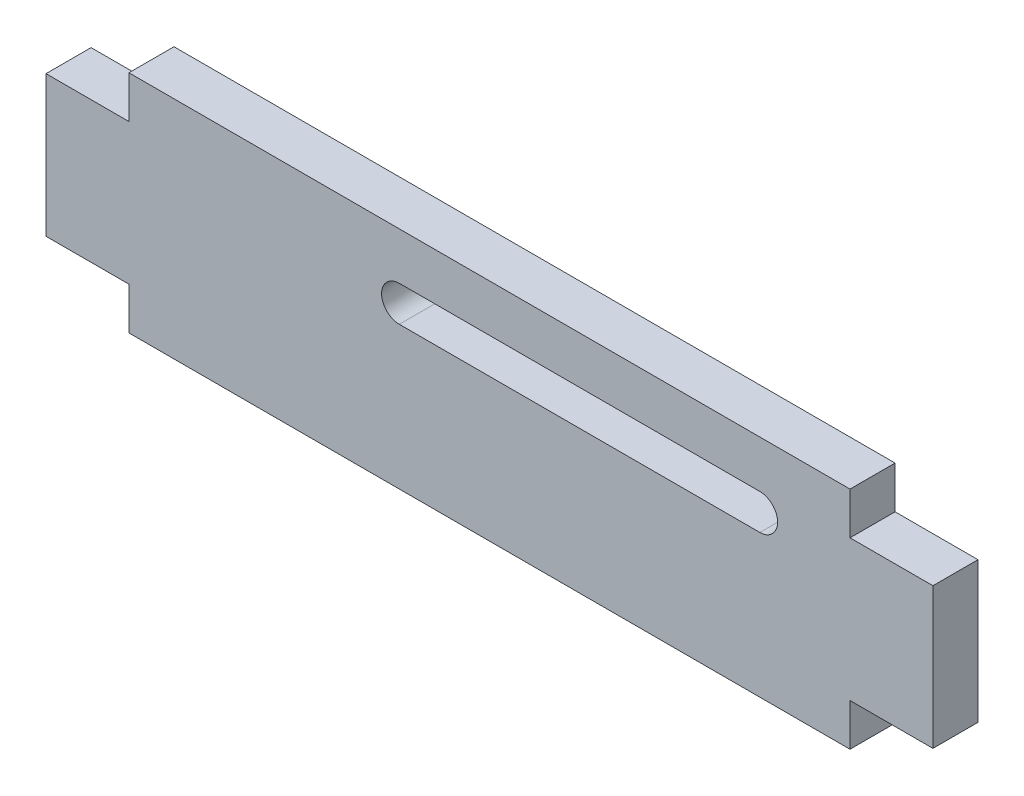
SolidWorks part; units mm, degrees
ref_plane "Front Plane" through (0, 0, 0) normal (0, 0, 1) x (1, 0, 0)
ref_plane "Top Plane" through (0, 0, 0) normal (0, 1, 0) x (1, 0, 0)
ref_plane "Right Plane" through (0, 0, 0) normal (1, 0, 0) x (0, 0, -1)
sketch "Sketch1" plane through (0, 0, 0) normal (0, 0, 1) x (1, 0, 0)
  line L0 (25.4, 0) -> (-25.4, 0) construction
  line L1 (-25.4, -7.9375) -> (25.4, -7.9375)
  line L2 (-6.35, 4.6155) -> (19.05, 4.6155)
  line L3 (-25.4, 7.9375) -> (25.4, 7.9375)
  line L4 (25.4, -7.9375) -> (25.4, -4.9625)
  line L5 (-25.4, -7.9375) -> (25.4, 7.9375) construction
  line L6 (-25.4, 7.9375) -> (25.4, -7.9375) construction
  line L7 (25.4, 4.9625) -> (25.4, 7.9375)
  line L8 (31.242, -4.9625) -> (25.4, -4.9625)
  line L9 (31.242, -4.9625) -> (31.242, 4.9625)
  line L10 (31.242, 4.9625) -> (25.4, 4.9625)
  line L11 (-31.242, 4.9625) -> (-25.4, -4.9625) construction
  line L12 (31.242, -4.9625) -> (25.4, 4.9625) construction
  line L13 (31.242, 4.9625) -> (25.4, -4.9625) construction
  line L14 (-31.242, -4.9625) -> (-25.4, 4.9625) construction
  line L15 (-31.242, 4.9625) -> (-25.4, 4.9625)
  line L16 (-31.242, -4.9625) -> (-31.242, 4.9625)
  line L17 (-31.242, -4.9625) -> (-25.4, -4.9625)
  line L18 (-25.4, 4.9625) -> (-25.4, 7.9375)
  line L19 (-25.4, -7.9375) -> (-25.4, -4.9625)
  line L20 (-10, -3.175) -> (-10, -3.125) construction
  line L21 (-19.05, 3.3655) -> (19.05, 3.3655) construction
  line L22 (10, 3.125) -> (10, 3.175) construction
  line L23 (10, -3.175) -> (10, -3.125) construction
  line L25 (-6.35, 2.1155) -> (19.05, 2.1155)
  line L26 (0, 0) -> (0, -7.9375) construction
  line L27 (-10, 3.125) -> (-10, 3.175) construction
  arc A1 (19.05, 2.1155) -> (19.05, 4.6155) centre (19.05, 3.3655) ccw
  arc A2 (-6.35, 4.6155) -> (-6.35, 2.1155) centre (-6.35, 3.3655) ccw
  point P0 (0, 0)
  point P8 (28.321, 0)
  point P19 (-28.321, 0)
  point P22 (-10, 0)
  point P29 (10, 0)
  point P30 (0, 3.3655)
  dimension "D5" = 1.25
  dimension "D11" = 6.35
  dimension "D1" = 50.8
  dimension "D2" = 15.875
  dimension "D3" = 5.842
  dimension "D4" = 9.925
  dimension "D6" = 6.35
  dimension "D7" = 10
  dimension "D8" = 38.1
  dimension "D9" = 4.572
  dimension "D10" = 25.4
extrude "Boss-Extrude1" add sketch "Sketch1" along normal blind 3.175
